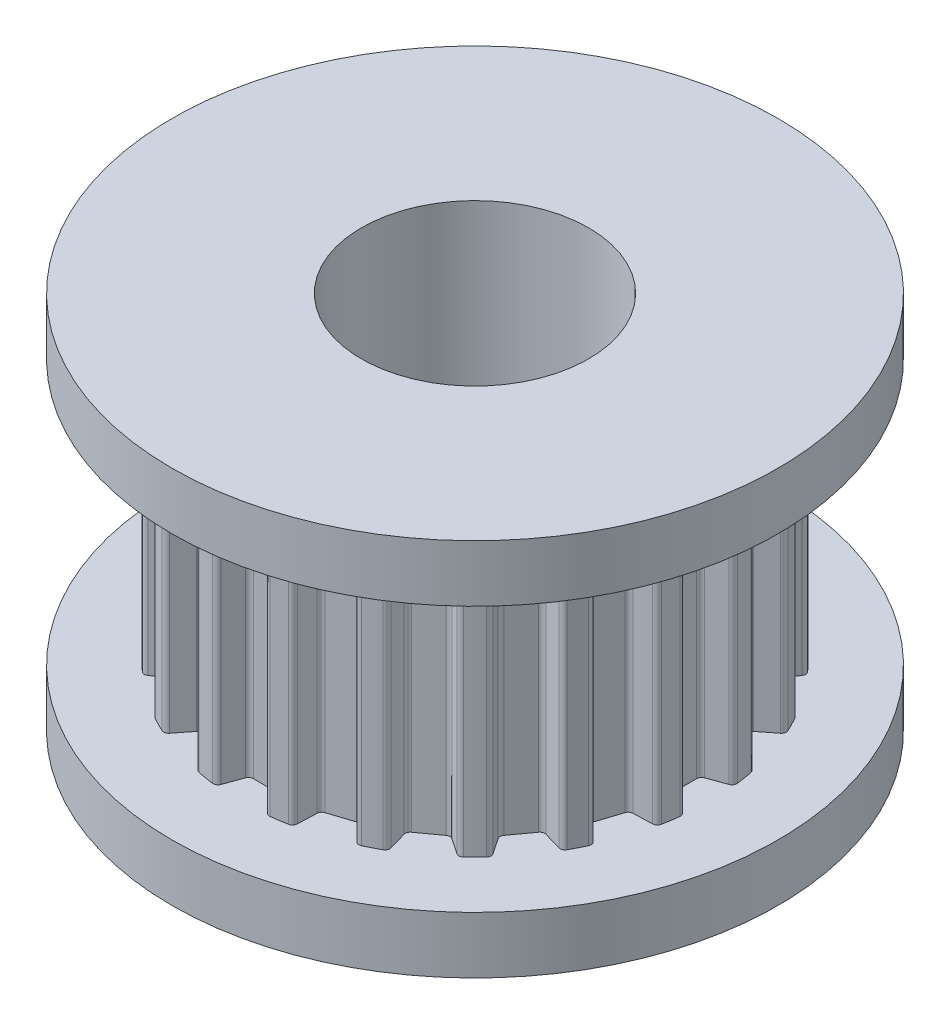
SolidWorks part; units mm, degrees
ref_plane "Front Plane" through (0, 0, 0) normal (0, 0, 1) x (1, 0, 0)
ref_plane "Top Plane" through (0, 0, 0) normal (0, 1, 0) x (1, 0, 0)
ref_plane "Right Plane" through (0, 0, 0) normal (1, 0, 0) x (0, 0, -1)
sketch "草圖1" plane through (0, 0, 0) normal (0, 1, 0) x (1, 0, 0)
  circle A0 centre (0, 0) radius 6.215
  dimension "D1" = 12.43
extrude "填料-伸長1" add sketch "草圖1" along normal blind 3.5 and the other way blind 3.5 contours A0
sketch "草圖2" plane through (0, -3.5, 0) normal (0, -1, 0) x (1, 0, 0)
  line L0 (0, 6.215) -> (0, 0) construction
  line L1 (0, 5.525) -> (-0.42, 5.525)
  line L2 (-0.42, 5.525) -> (-0.6584, 6.18)
  line L3 (0, 5.525) -> (0.42, 5.525)
  line L4 (0.42, 5.525) -> (0.6584, 6.18)
  circle A0 centre (0, 0) radius 6.215 construction
  arc A1 (-0.6584, 6.18) -> (0.6584, 6.18) centre (0, 0) cw
  circle M7 centre (0, 0) radius 6.215
  dimension "D1" = 0.69
  dimension "D2" = 0.84
  dimension "D3" = 40
extrude "除料-伸長1" cut sketch "草圖2" against normal through all contours L0 A1 L2 L1 | L0 L3 L4 M7 region at (0.2729, -3.5, 5.8899) region at (-0.2729, -3.5, 5.8899)
fillet "圓角1" radius 0.13 4 edges at (-0.6584, 0, 6.18) (0.6584, 0, 6.18) (0.42, 0, 5.525) (-0.42, 0, 5.525)
pattern_circular "環狀複製排列1" count 20 over 360 about axis through (0, -3.5, 0) along (0, 1, 0) of "圓角1", "除料-伸長1"
sketch "草圖3" plane through (0, 3.5, 0) normal (0, 1, 0) x (1, 0, 0)
  circle A0 centre (0, 0) radius 8
  dimension "D1" = 16
extrude "填料-伸長2" add sketch "草圖3" along normal blind 1.5
sketch "草圖4" plane through (0, -3.5, 0) normal (0, -1, 0) x (1, 0, 0)
  circle A0 centre (0, 0) radius 8
  circle A1 centre (0, 0) radius 8 construction
extrude "填料-伸長3" add sketch "草圖4" along normal blind 1.5
sketch "草圖5" plane through (0, -5, 0) normal (0, -1, 0) x (1, 0, 0)
  circle A0 centre (0, 0) radius 3
  dimension "D1" = 6
extrude "除料-伸長2" cut sketch "草圖5" against normal through all and the other way through all
